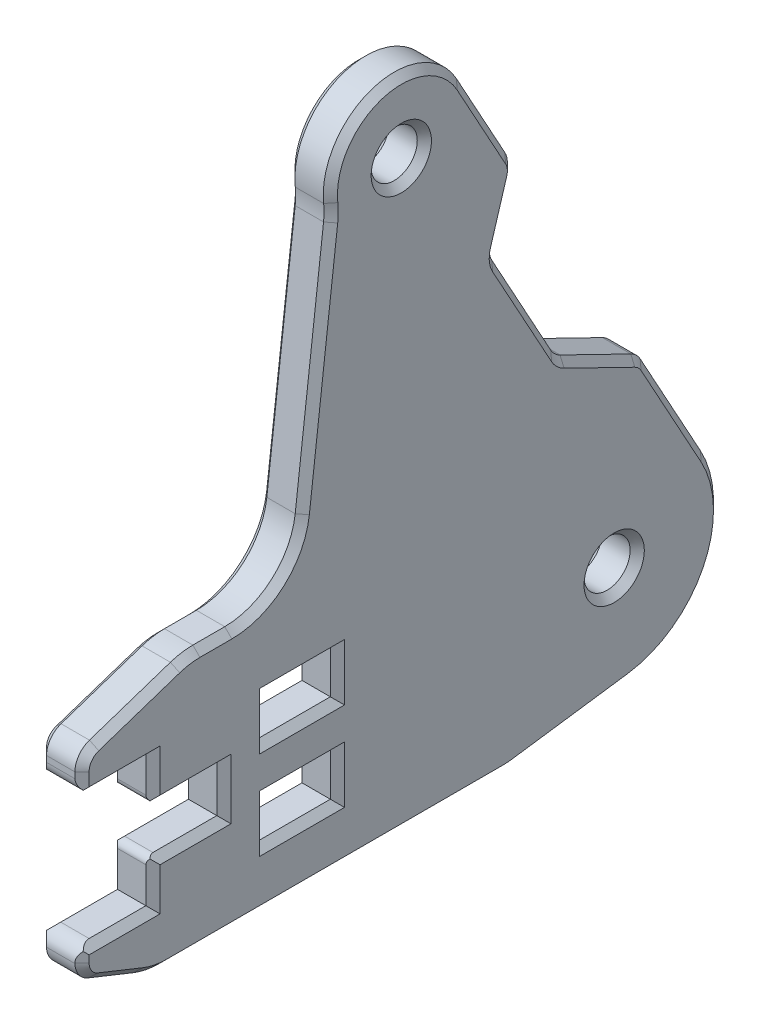
SolidWorks part; units mm, degrees
ref_plane "前视基准面" through (0, 0, 0) normal (0, 0, 1) x (1, 0, 0)
ref_plane "上视基准面" through (0, 0, 0) normal (0, 1, 0) x (1, 0, 0)
ref_plane "右视基准面" through (0, 0, 0) normal (1, 0, 0) x (0, 0, -1)
ref_plane "基准面1" through (1.5, 0, 0) normal (1, 0, 0) x (0, 0, -1)
sketch "草图1" plane through (1.5, 0, 0) normal (1, 0, 0) x (0, 0, -1)
  line L0 (-19.5, 1.625) -> (-24.5, 1.625)
  line L1 (-24.5, 1.625) -> (-24.5, 4.625)
  line L2 (-24.5, 4.625) -> (-19.5, 4.625)
  line L3 (-19.5, 4.625) -> (-19.5, 1.625)
  line L4 (-24.5, -1.625) -> (-19.5, -1.625)
  line L5 (-19.5, -1.625) -> (-19.5, -4.625)
  line L6 (-19.5, -4.625) -> (-24.5, -4.625)
  line L7 (-24.5, -4.625) -> (-24.5, -1.625)
  line L8 (-9.962, 5.4767) -> (-17.2955, 21.366)
  line L9 (-14.1176, 22.8327) -> (-6.7841, 6.9434)
  line L10 (-7.1545, -8.5766) -> (1.0414, -7.4273)
  line L11 (6.5736, 3.6109) -> (2.332, 11.3325)
  line L12 (1.6745, 11.9587) -> (-3.312, 14.3892)
  line L13 (-3.9695, 15.0154) -> (-8.1202, 22.5717)
  line L14 (-8.2414, 23.7276) -> (-7.0881, 27.5466)
  line L15 (-7.2093, 28.7024) -> (-10.6176, 34.9072)
  line L16 (-19.9775, 30.8393) -> (-21.9757, 14.0346)
  line L17 (-26.9407, 9.625) -> (-29.1886, 9.625)
  line L18 (-30.7698, 9.3684) -> (-36.4743, 7.4669)
  line L19 (-37.5, 6.0439) -> (-37.5, 4.625)
  line L20 (-37.5, 4.625) -> (-32.5, 4.625)
  line L21 (-32.5, 4.625) -> (-32.5, 1.625)
  line L22 (-32.5, 1.625) -> (-27.5, 1.625)
  line L23 (-27.5, 1.625) -> (-27.5, -1.625)
  line L24 (-27.5, -1.625) -> (-32.5, -1.625)
  line L25 (-32.5, -1.625) -> (-32.5, -4.625)
  line L26 (-32.5, -4.625) -> (-37.5, -4.625)
  line L27 (-37.5, -4.625) -> (-37.5, -5.6095)
  line L28 (-36.5571, -7.0022) -> (-33.394, -8.2674)
  line L29 (-31.5371, -8.625) -> (-7.8488, -8.625)
  circle A0 centre (-15, 32.5) radius 1.625
  circle A1 centre (0, 0) radius 1.625
  arc A2 (-6.7841, 6.9434) -> (-9.962, 5.4767) centre (-8.373, 6.2101) cw
  arc A3 (-17.2955, 21.366) -> (-14.1176, 22.8327) centre (-15.7066, 22.0994) cw
  arc A4 (1.0414, -7.4273) -> (6.5736, 3.6109) centre (0, 0) ccw
  arc A5 (2.332, 11.3325) -> (1.6745, 11.9587) centre (1.0173, 10.6103) ccw
  arc A6 (-3.312, 14.3892) -> (-3.9695, 15.0154) centre (-2.6548, 15.7376) cw
  arc A7 (-8.1202, 22.5717) -> (-8.2414, 23.7276) centre (-6.8055, 23.2939) cw
  arc A8 (-7.0881, 27.5466) -> (-7.2093, 28.7024) centre (-8.524, 27.9803) ccw
  arc A9 (-10.6176, 34.9072) -> (-19.9713, 31.9649) centre (-15, 32.5) ccw
  arc A10 (-19.9713, 31.9649) -> (-19.9775, 30.8393) centre (-24.9426, 31.4297) cw
  arc A11 (-21.9757, 14.0346) -> (-26.9407, 9.625) centre (-26.9407, 14.625) cw
  arc A12 (-29.1886, 9.625) -> (-30.7698, 9.3684) centre (-29.1886, 4.625) ccw
  arc A13 (-36.4743, 7.4669) -> (-37.5, 6.0439) centre (-36, 6.0439) ccw
  arc A14 (-37.5, -5.6095) -> (-36.5571, -7.0022) centre (-36, -5.6095) ccw
  arc A15 (-33.394, -8.2674) -> (-31.5371, -8.625) centre (-31.5371, -3.625) ccw
  arc A16 (-7.8488, -8.625) -> (-7.1545, -8.5766) centre (-7.8488, -3.625) ccw
  dimension "D1" = 3.25
  dimension "D3" = 5
  dimension "D6" = 7.5
  dimension "D7" = 3.25
  dimension "D9" = 1.75
  dimension "D16" = 5
  dimension "D19" = 1.5
  dimension "D21" = 5
  dimension "D2" = 7.0793
  dimension "D4" = 8.6213
  dimension "D5" = 8.8099
  dimension "D8" = 17.5
  dimension "D10" = 5
  dimension "D11" = 3
  dimension "D12" = 5
  dimension "D13" = 3.25
  dimension "D14" = 3
  dimension "D15" = 5
  dimension "D17" = 16.8047
  dimension "D18" = 6.0132
  dimension "D20" = 1.4189
  dimension "D22" = 23.6883
  dimension "D23" = 8.196
extrude "凸台-拉伸1" add sketch "草图1" against normal blind 3
chamfer "倒角1" distance 0.5 angle 45 94 edges at (-1.5, -8.002, 3.0565) (-1.5, -3.3604, -6.705) (-1.5, 7.4717, -4.4528) (-1.5, 11.6965, -2.0518) (-1.5, 13.174, 0.8187) (-1.5, 14.6514, 3.6893) (-1.5, 18.7936, 6.0449) (-1.5, 23.1374, 8.2973) (-1.5, 25.6371, 7.6648) (-1.5, 28.1367, 7.0322) (-1.5, 31.8048, 8.9135) (-1.5, 37.2696, 16.5004) (-1.5, 31.4019, 19.9426) (-1.5, 22.437, 20.9766) (-1.5, 10.8866, 23.6204) (-1.5, 9.625, 28.0647) (-1.5, 9.5604, 29.9895) (-1.5, 8.4177, 33.622) (-1.5, 6.9209, 37.2169) (-1.5, 5.3344, 37.5) (-1.5, 4.625, 35) (-1.5, 3.125, 32.5) (-1.5, 1.625, 30) (-1.5, 0, 27.5) (-1.5, -1.625, 30) (-1.5, -3.125, 32.5) (-1.5, -4.625, 35) (-1.5, -5.1172, 37.5) (-1.5, -6.4504, 37.2421) (-1.5, -7.6348, 34.9756) (-1.5, -8.5348, 32.4826) (-1.5, -8.625, 19.693) (-1.5, -8.6129, 7.5008) (-1.5, 32.5, 16.625) (-1.5, 0, 1.625) (-1.5, 3.125, 24.5) (-1.5, 4.625, 22) (-1.5, 3.125, 19.5) (-1.5, 1.625, 22) (-1.5, -3.125, 19.5) (-1.5, -4.625, 22) (-1.5, -3.125, 24.5) (-1.5, -1.625, 22) (-1.5, 23.6883, 16.4399) (-1.5, 14.8881, 10.4509) (-1.5, 4.6211, 7.6397) (-1.5, 13.4214, 13.6287) (1.5, -8.625, 19.693) (1.5, -8.5348, 32.4826) (1.5, -7.6348, 34.9756) (1.5, -6.4504, 37.2421) (1.5, -5.1172, 37.5) (1.5, -4.625, 35) (1.5, -3.125, 32.5) (1.5, -1.625, 30) (1.5, 0, 27.5) (1.5, 1.625, 30) (1.5, 3.125, 32.5) (1.5, 4.625, 35) (1.5, 5.3344, 37.5) (1.5, 6.9209, 37.2169) (1.5, 8.4177, 33.622) (1.5, 9.5604, 29.9895) (1.5, 9.625, 28.0647) (1.5, 10.8866, 23.6204) (1.5, 22.437, 20.9766) (1.5, 31.4019, 19.9426) (1.5, 37.2696, 16.5004) (1.5, 31.8048, 8.9135) (1.5, 28.1367, 7.0322) (1.5, 25.6371, 7.6648) (1.5, 23.1374, 8.2973) (1.5, 18.7936, 6.0449) (1.5, 14.6514, 3.6893) (1.5, 13.174, 0.8187) (1.5, 11.6965, -2.0518) (1.5, 7.4717, -4.4528) (1.5, -3.3604, -6.705) (1.5, -8.002, 3.0565) (1.5, -8.6129, 7.5008) (1.5, 32.5, 16.625) (1.5, 0, 1.625) (1.5, 4.625, 22) (1.5, 3.125, 24.5) (1.5, 1.625, 22) (1.5, 3.125, 19.5) (1.5, -4.625, 22) (1.5, -3.125, 19.5) (1.5, -1.625, 22) (1.5, -3.125, 24.5) (1.5, 14.8881, 10.4509) (1.5, 23.6883, 16.4399) (1.5, 13.4214, 13.6287) (1.5, 4.6211, 7.6397)
fillet "圆角1" radius 1 2 edges at (0, -4.625, 37.5) (0, 4.625, 37.5)
fillet "圆角2" radius 0.5 2 edges at (0, -1.625, 32.5) (0, 1.625, 32.5)
sketch3d "3D草图1"
  line L0 (1.5, 22.8919, 19.1563) -> (1.5, 6.0714, 15.6137)
  line L1 (1.5, 6.0714, 15.6137) -> (1.5, -0.5265, 4.8)
  line L2 (1.5, -0.5265, 4.8) -> (1.5, 10.462, 2.0127)
  line L3 (1.5, 10.462, 2.0127) -> (1.5, 20.4973, 11.0508)
  line L4 (1.5, 20.4973, 11.0508) -> (1.5, 27.8305, 13.2042)
  line L5 (1.5, 27.8305, 13.2042) -> (1.5, 25.4161, 17.385)
  line L6 (1.5, 25.4161, 17.385) -> (1.5, 22.8919, 19.1563)
extrude "凸台-拉伸2" add sketch "3D草图1" along direction (1, 0, 0) on the side against the normal blind 3
